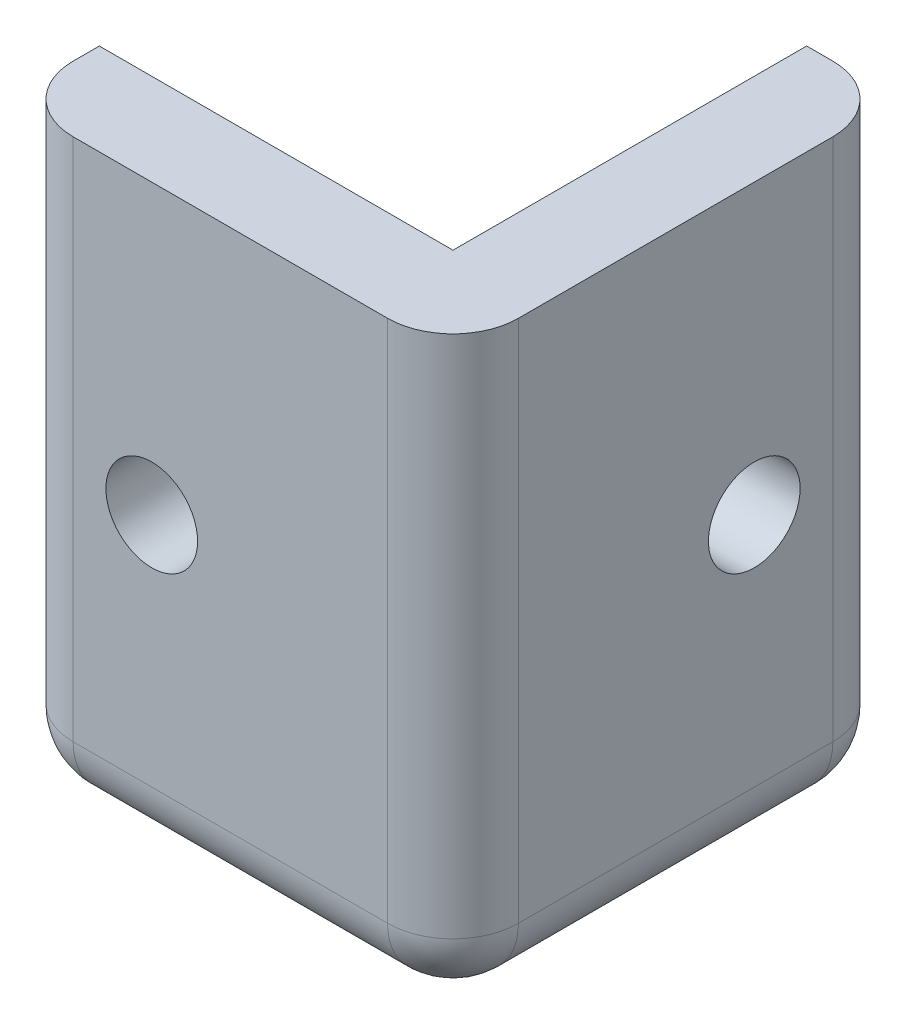
SolidWorks part; units mm, degrees
ref_plane "Alzado" through (0, 0, 0) normal (0, 0, 1) x (1, 0, 0)
ref_plane "Planta" through (0, 0, 0) normal (0, 1, 0) x (1, 0, 0)
ref_plane "Vista lateral" through (0, 0, 0) normal (1, 0, 0) x (0, 0, -1)
sketch "Croquis1" plane through (0, 0, 0) normal (0, 1, 0) x (1, 0, 0)
  line L0 (0, 0) -> (27, 0)
  line L1 (27, 0) -> (27, 27)
  line L2 (0, -7) -> (34, -7)
  line L3 (34, -7) -> (34, 27)
  line L4 (0, 0) -> (0, -7)
  line L5 (27, 27) -> (34, 27)
  dimension "D1" = 27
  dimension "D2" = 27
  dimension "D3" = 7
extrude "Saliente-Extruir1" add sketch "Croquis1" along normal blind 28
sketch "Croquis2" plane through (0, 0, 0) normal (0, -1, 0) x (-1, 0, 0)
  line L0 (-34, 27) -> (-27, 27) construction
  line L1 (-34, -7) -> (0, -7)
  line L2 (-34, -7) -> (-34, 27)
  line L3 (-34, 27) -> (0, 27)
  line L4 (0, -7) -> (0, 27)
  line L6 (0, 0) -> (0, -7) construction
extrude "Saliente-Extruir2" add sketch "Croquis2" along normal blind 7
fillet "Redondeo1" radius 5 5 edges at (17, -7, 7) (34, -7, -10) (34, 10.5, -27) (0, 10.5, 7) (34, 10.5, 7)
sketch "Croquis3" plane through (34, 0, 0) normal (1, 0, 0) x (0, 0, -1)
  line L0 (-7, -2) -> (-7, 28) construction
  line L1 (27, -7) -> (-2, -7) construction
  circle A0 centre (16, 16) radius 3.5
  dimension "D1" = 7
  dimension "D2" = 23
  dimension "D3" = 23
extrude "Cortar-Extruir1" cut sketch "Croquis3" against normal blind 5
sketch "Croquis4" plane through (29, 0, 0) normal (1, 0, 0) x (0, 0, -1)
  circle A0 centre (16, 16) radius 2
  dimension "D1" = 4
extrude "Cortar-Extruir2" cut sketch "Croquis4" against normal blind 5
sketch "Croquis5" plane through (0, 0, 7) normal (0, 0, 1) x (1, 0, 0)
  line L0 (34, 28) -> (34, -2) construction
  line L1 (29, -7) -> (0, -7) construction
  circle A0 centre (11, 16) radius 3.5
  dimension "D1" = 7
  dimension "D2" = 23
  dimension "D3" = 23
extrude "Cortar-Extruir3" cut sketch "Croquis5" against normal blind 5
sketch "Croquis6" plane through (0, 0, 2) normal (0, 0, 1) x (1, 0, 0)
  circle A0 centre (11, 16) radius 2
  dimension "D1" = 4
extrude "Cortar-Extruir4" cut sketch "Croquis6" against normal blind 5
fillet "Redondeo2" radius 5 4 edges at (32.5355, -5.5355, -25.5355) (1.4645, -5.5355, 5.5355) (14.5, -7, -27) (0, -7, -12.5)
sketch "Croquis7" plane through (0, 28, 0) normal (0, 1, 0) x (1, 0, 0)
  line L6 (34, -2) -> (34, 22)
  line L7 (29, 27) -> (27, 27)
  line L8 (27, 27) -> (27, 0)
  line L9 (27, 0) -> (0, 0)
  line L10 (0, 0) -> (0, -2)
  line L11 (5, -7) -> (29, -7)
  line L12 (34, -2) -> (34, 22)
  line L13 (29, 27) -> (27, 27)
  line L14 (27, 27) -> (27, 0)
  line L15 (27, 0) -> (0, 0)
  line L16 (0, 0) -> (0, -2)
  line L17 (5, -7) -> (29, -7)
  arc A3 (34, 22) -> (29, 27) centre (29, 22) ccw
  arc A4 (0, -2) -> (5, -7) centre (5, -2) ccw
  arc A5 (29, -7) -> (34, -2) centre (29, -2) ccw
  arc A6 (34, 22) -> (29, 27) centre (29, 22) ccw
  arc A7 (0, -2) -> (5, -7) centre (5, -2) ccw
  arc A8 (29, -7) -> (34, -2) centre (29, -2) ccw
  dimension "D1" = 0
extrude "Saliente-Extruir3" add sketch "Croquis7" along normal blind 10
